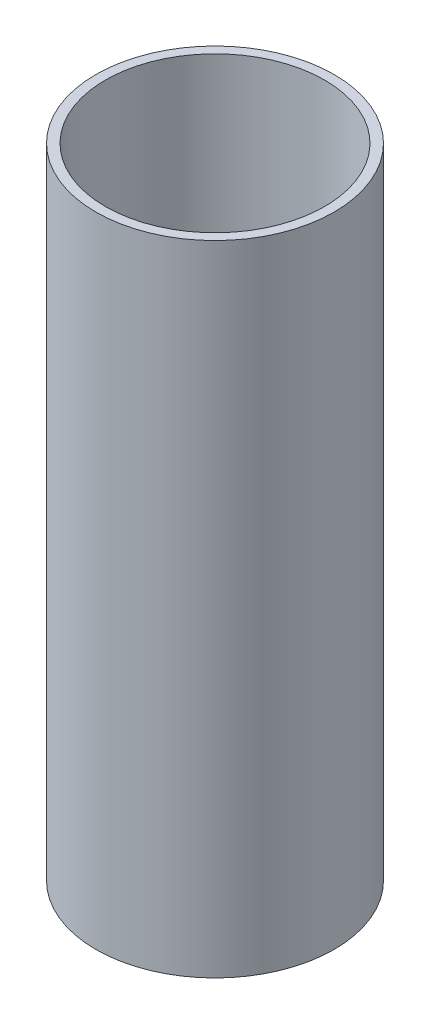
SolidWorks part; units mm, degrees
ref_plane "Front Plane" through (0, 0, 0) normal (0, 0, 1) x (1, 0, 0)
ref_plane "Top Plane" through (0, 0, 0) normal (0, 1, 0) x (1, 0, 0)
ref_plane "Right Plane" through (0, 0, 0) normal (1, 0, 0) x (0, 0, -1)
sketch "Sketch1" plane through (0, 0, 0) normal (0, 1, 0) x (1, 0, 0)
  circle A0 centre (0, 0) radius 11.5
  circle A1 centre (0, 0) radius 12.5
  dimension "D1" = 23
  dimension "D2" = 25
extrude "Boss-Extrude1" add sketch "Sketch1" along normal blind 67
